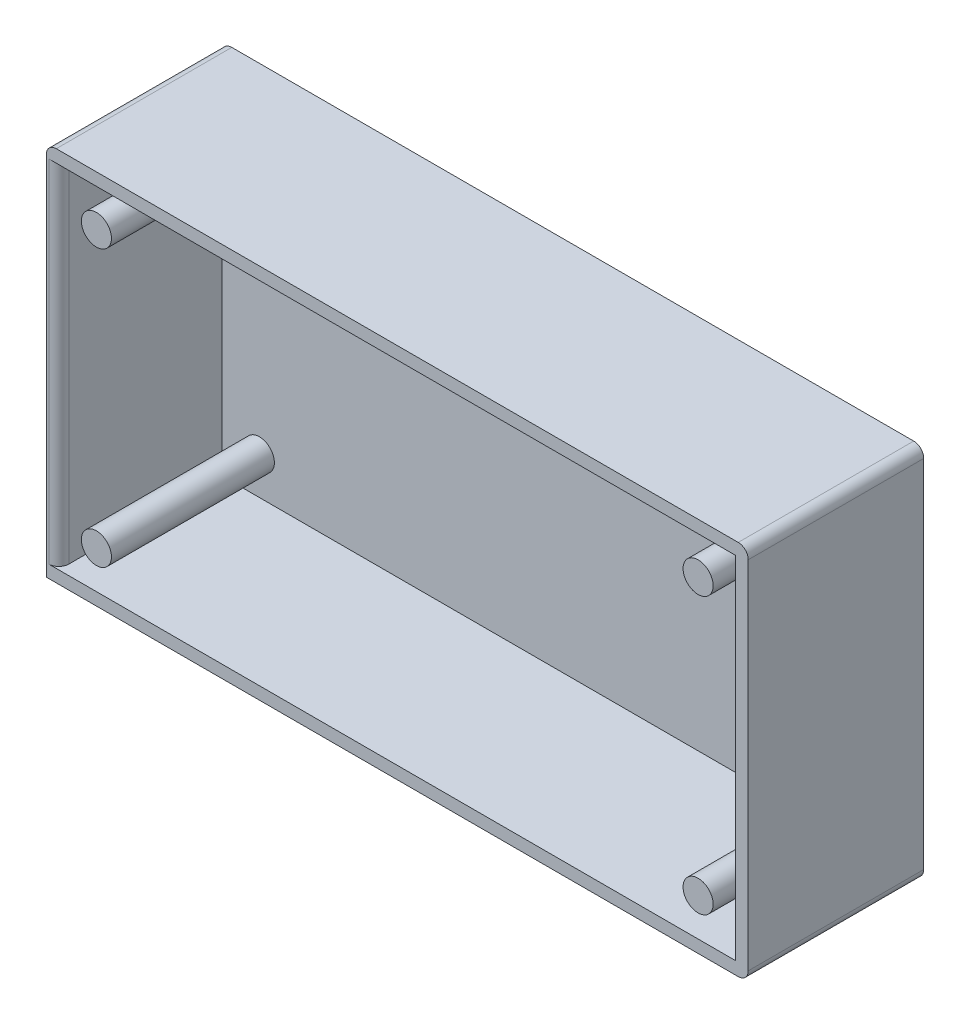
SolidWorks part; units mm, degrees
ref_plane "前视基准面" through (0, 0, 0) normal (0, 0, 1) x (1, 0, 0)
ref_plane "上视基准面" through (0, 0, 0) normal (0, 1, 0) x (1, 0, 0)
ref_plane "右视基准面" through (0, 0, 0) normal (1, 0, 0) x (0, 0, -1)
other "Configuration Table"
sketch "Sketch1" plane through (0, 0, 0) normal (0, 0, 1) x (1, 0, 0)
  line L1 (-70, -37.5) -> (70, -37.5)
  line L2 (-70, -37.5) -> (-70, 37.5)
  line L3 (-70, 37.5) -> (70, 37.5)
  line L4 (70, -37.5) -> (70, 37.5)
  line L5 (-70, -37.5) -> (70, 37.5) construction
  line L6 (-70, 37.5) -> (70, -37.5) construction
  point P0 (0, 0)
extrude "Boss-Extrude1" add sketch "Sketch1" along normal blind 35
shell "Shell1" thickness 2.5 removed face at (0, 0, 35)
ref_plane "Plane1" through (0, 0, 2.5) normal (0, 0, 1) x (1, 0, 0)
sketch "Sketch2" plane through (0, 0, 2.5) normal (0, 0, 1) x (1, 0, 0)
  circle A0 centre (-60, -27.5) radius 3
  circle A1 centre (60, -27.5) radius 3
  circle A2 centre (-60, 27.5) radius 3
  circle A3 centre (60, 27.5) radius 3
extrude "Boss-Extrude2" add sketch "Sketch2" along normal blind 32.5
sketch "Sketch3" plane through (0, 0, 0) normal (0, 0, 1) x (1, 0, 0)
  circle A0 centre (-65, -32.5) radius 2.25
  circle A1 centre (65, -32.5) radius 2.5
  circle A2 centre (-65, 32.5) radius 2.25
  circle A3 centre (65, 32.5) radius 2.5
extrude "Cut-Extrude1" cut sketch "Sketch3" along normal blind 35
sketch "Sketch4" plane through (0, 0, 2.5) normal (0, 0, 1) x (1, 0, 0)
  line L0 (67.5, -32.5) -> (67.5, 32.5) construction
  line L1 (-67.5, -1.5) -> (67.5, -1.5)
  line L2 (-67.5, -1.5) -> (-67.5, 1.5)
  line L3 (-67.5, 1.5) -> (67.5, 1.5)
  line L4 (67.5, -1.5) -> (67.5, 1.5)
  line L5 (-67.5, -1.5) -> (67.5, 1.5) construction
  line L6 (-67.5, 1.5) -> (67.5, -1.5) construction
  line L7 (67.5, 35) -> (-67.5, 35) construction
  line L8 (-0.7778, -35) -> (0.7778, -35)
  line L9 (-0.7778, -35) -> (-0.7778, 35)
  line L10 (-0.7778, 35) -> (0.7778, 35)
  line L11 (0.7778, -35) -> (0.7778, 35)
  line L12 (-0.7778, -35) -> (0.7778, 35) construction
  line L13 (-0.7778, 35) -> (0.7778, -35) construction
  point P0 (0, 0)
  point P8 (0, 0)
fillet "Fillet1" radius 2 4 edges at (70, 37.5, 17.5) (-70, 37.5, 17.5) (70, -37.5, 17.5) (-67.5, 0, 35)
ref_plane "face_top_inner" through (0, 0, 35) normal (0, 0, 1) x (1, 0, 0)
ref_plane "face_inner_bottom" through (0, 0, 2.5) normal (0, 0, 1) x (1, 0, 0)
ref_plane "face_bottom_outer" through (0, 0, 0) normal (0, 0, 1) x (1, 0, 0)
sketch3d "3DSketch1"
  line L0 (-60, -27.5, 2.5) -> (-60, -27.5, 35) construction
ref_axis "axis_screw_post_1" through (-60, -27.5, 2.5) along (0, 0, 1)
sketch3d "3DSketch2"
  line L0 (60, -27.5, 2.5) -> (60, -27.5, 35) construction
ref_axis "axis_screw_post_2" through (60, -27.5, 2.5) along (0, 0, 1)
sketch3d "3DSketch3"
  line L0 (-60, 27.5, 2.5) -> (-60, 27.5, 35) construction
ref_axis "axis_screw_post_3" through (-60, 27.5, 2.5) along (0, 0, 1)
sketch3d "3DSketch4"
  line L0 (60, 27.5, 2.5) -> (60, 27.5, 35) construction
ref_axis "axis_screw_post_4" through (60, 27.5, 2.5) along (0, 0, 1)
